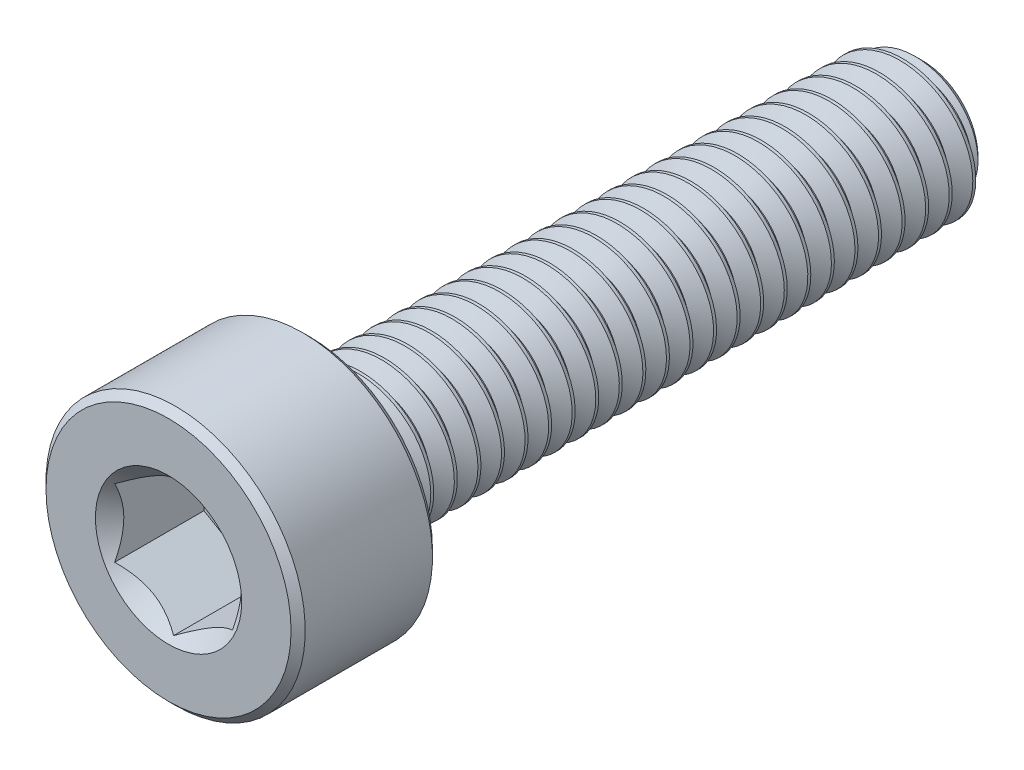
SolidWorks part; units mm, degrees
ref_plane "Front Plane" through (0, 0, 0) normal (0, 0, 1) x (1, 0, 0)
ref_plane "Top Plane" through (0, 0, 0) normal (0, 1, 0) x (1, 0, 0)
ref_plane "Right Plane" through (0, 0, 0) normal (1, 0, 0) x (0, 0, -1)
sketch "Sketch1" plane through (0, 0, 0) normal (1, 0, 0) x (0, 0, -1)
  line L0 (-8, 0) -> (8, 0) construction
  line L1 (8, 0) -> (8, 1.1752) construction
  line L2 (8, 1.1752) -> (7.6752, 1.5) construction
  line L3 (7.6752, 1.5) -> (7.625, 1.5) construction
  line L4 (7.625, 1.5) -> (-5, 1.5) construction
  line L5 (-5, 1.5) -> (-5, 2.75) construction
  line L6 (-5, 2.75) -> (-8, 2.75) construction
  line L7 (-8, 2.75) -> (-8, 0) construction
  line L8 (8, 1.1752) -> (8, 1.5) construction
  line L9 (7.9688, 1.5541) -> (8.2188, 1.1211) construction
  line L10 (8.2188, 1.1211) -> (8.4688, 1.5541) construction
  line L11 (8.4688, 1.5541) -> (7.9688, 1.5541) construction
  line L12 (8.2188, 1.5541) -> (8.2188, 1.5) construction
  line L13 (8.2188, 1.1211) -> (8.2188, 1.1752) construction
  line L14 (8.1875, 1.1752) -> (8.25, 1.1752) construction
  line L15 (8, 1.5) -> (8.4375, 1.5) construction
  line L16 (7.9844, 1.5271) -> (8.4531, 1.5271) construction
  line L17 (8, 0) -> (8, -1.5) construction
  line L18 (-5.15, 2.75) -> (-5, 2.6) construction
  line L19 (-7.85, 2.75) -> (-8, 2.6) construction
  line L20 (-5, 1.5) -> (-5, 0) construction
  line L21 (-5, 0.75) -> (-0.6667, 0.75) construction
  line L22 (-0.6667, 0.75) -> (3.6667, 0.75) construction
  line L23 (3.6667, 0.75) -> (8, 0.75) construction
  line L24 (-0.6667, 0.75) -> (-0.6667, 1.5) construction
  line L25 (-0.6667, 1.5) -> (-0.6667, 2.75) construction
  line L26 (3.6667, 0.75) -> (3.6667, 2.75) construction
  point P0 (-8, 1.25)
  point P3 (6.75, 1.5)
  point P4 (0, 0)
  point P18 (3.6667, 1.5)
  point P22 (8.2188, 1.1752)
  point P24 (7.625, 1.5)
  point P25 (8.2188, 1.5)
  point P28 (8.2188, 1.5271)
  point P29 (6.75, -1.5)
  point P30 (-0.6667, 1.5)
  point P31 (-6.5, 2.75)
  point P37 (-5.525, 2.75)
  point P38 (-7.775, 2.75)
  point P45 (-0.6667, 0.75)
  point P46 (3.6667, 0.75)
  dimension "D2" = 0.0625
  dimension "D7" = 0.15
  dimension "D8" = 0.15
  dimension "D9" = 0.15
  dimension "D10" = 0.075
  dimension "D11" = 0.375
  dimension "Drive Size" = 2.5
  dimension "Head Diameter" = 5.5
  dimension "Head Height" = 3
  dimension "Thread Pitch" = 0.5
  dimension "Thread Dia" = 3
  dimension "Length" = 13
  dimension "D12" = 0.375
  dimension "D4" = 1.25
  dimension "D3" = 45
sketch "Sketch2" plane through (0, 0, 0) normal (1, 0, 0) x (0, 0, -1)
  line L0 (-8, 0) -> (-8, 2.6)
  line L1 (-7.85, 2.75) -> (-5.15, 2.75)
  line L2 (-5, 2.6) -> (-5, 1.65)
  line L4 (7.6752, 1.5) -> (8, 1.1752)
  line L5 (8, 1.1752) -> (8, 0)
  line L6 (-5, 2.75) -> (-8, 2.75) construction
  line L7 (8, 0) -> (-8, 0)
  line L8 (-7.85, 2.75) -> (-8, 2.6) construction
  line L10 (-7.85, 2.75) -> (-8, 2.6)
  line L14 (-5.15, 2.75) -> (-5, 2.6) construction
  line L16 (-5.15, 2.75) -> (-5, 2.6)
  line L17 (-5, 1.5) -> (-5, 2.75) construction
  line L19 (-4.85, 1.5) -> (7.6752, 1.5)
  line L20 (7.625, 1.5) -> (-5, 1.5) construction
  arc A1 (-5, 1.65) -> (-4.85, 1.5) centre (-4.85, 1.65) ccw
  dimension "D3" = 0.15
revolve "Revolve1" add sketch "Sketch2" angle 360 about L7
sketch "Sketch3" plane through (0, 0, 8) normal (0, 0, 1) x (1, 0, 0)
  line L1 (1.25, -0.7217) -> (1.25, 0.7217)
  line L2 (1.25, 0.7217) -> (0, 1.4434)
  line L3 (0, 1.4434) -> (-1.25, 0.7217)
  line L4 (-1.25, 0.7217) -> (-1.25, -0.7217)
  line L5 (-1.25, -0.7217) -> (0, -1.4434)
  line L6 (0, -1.4434) -> (1.25, -0.7217)
  circle A0 centre (0, 0) radius 1.25 construction
  circle A1 centre (0, 0) radius 2.75 construction
  circle A2 centre (0, 0) radius 2.75 construction
  circle A3 centre (0, 0) radius 1.4434 construction
  point P13 (0, 0)
  dimension "D1" = 2.8868
extrude "Cut-Extrude1" cut sketch "Sketch3" against normal offset from surface (2 mm away) 1 up to face at (0, 2.6, 5)
sketch "Sketch4" plane through (0, 0, 8) normal (0, 0, 1) x (1, 0, 0)
  circle A0 centre (0, 0) radius 1.5516
  dimension "D1" = 3.1033
extrude "Cut-Extrude2" cut sketch "Sketch4" against normal up to vertex (1.5 mm away) draft 45 up to point (0, 2.75, 6.5)
sketch "Sketch11" plane through (0, 0, 0) normal (1, 0, 0) x (0, 0, -1)
  line L0 (-8, 0) -> (8, 0) construction
  line L1 (-8, 0) -> (8, 0) construction
  line L2 (-2.5625, 0) -> (-2.5625, 1.5) construction
  line L3 (7.625, 1.5) -> (-5, 1.5) construction
  line L4 (5.5625, 0) -> (5.5625, 1.5) construction
  line L6 (8, 1.1752) -> (8, 1.5) construction
  point P2 (-2.5625, 0)
  point P3 (5.5625, 0)
  dimension "D1" = 2.4375
  dimension "D2" = 2.4375
sketch "Sketch6" plane through (0, 0, -8) normal (0, 0, -1) x (-1, 0, 0)
  circle A0 centre (0, 0) radius 1.5
curve "Helix/Spiral1" pitch 0.5 height 13.5 radius 1.5 centre (0, 0, -8) axis (0, 0, 1) start towards (0, 1, 0)
sketch "Sketch10" plane through (0, 0, 0) normal (1, 0, 0) x (0, 0, -1)
  line L0 (-4.85, -2.75) -> (-4.85, 2.75)
  line L5 (-8, 0) -> (8, 0) construction
  line L6 (-4.85, 1.5) -> (-4.85, -1.5) construction
  point P3 (-4.85, 0)
split "Split1" trim tools "Sketch10" bodies to split 106 resulting bodies 114 115
sketch "Sketch7" plane through (0, 0, 0) normal (1, 0, 0) x (0, 0, -1)
  line L0 (7.9844, 1.5271) -> (8.4531, 1.5271)
  line L1 (8.4531, 1.5271) -> (8.25, 1.1752)
  line L2 (8.25, 1.1752) -> (8.1875, 1.1752)
  line L3 (8.1875, 1.1752) -> (7.9844, 1.5271)
sweep "Cut-Sweep1" cut profiles "Sketch7" path "Helix/Spiral1" align with end faces yes
sketch "Sketch8" plane through (0, 0, 0) normal (1, 0, 0) x (0, 0, -1)
  line L0 (-5, 0) -> (-5, 1.5)
  line L1 (-4.85, -1.5) -> (-4.85, 1.5) construction
  line L2 (-5, 1.5) -> (-4.85, 1.5)
  line L4 (-4.85, 1.5) -> (-3.984, 0)
  line L5 (-3.984, 0) -> (-5, 0)
  line L6 (7.625, 1.5) -> (-5, 1.5) construction
  line L7 (-8, 0) -> (8, 0) construction
  dimension "D1" = 60
revolve "Revolve2" add sketch "Sketch8" angle 360 about L5
equation "\"D2@Sketch1\" = \"Thread Pitch@Sketch1\" / 8"
equation "\"D4@Helix/Spiral1\" = \"Thread Pitch@Sketch1\""
equation "\"D7@Sketch1\" = \"Head Height@Sketch1\" * .05"
equation "\"D8@Sketch1\"=\"D7@Sketch1\""
equation "\"D9@Sketch1\"=\"D7@Sketch1\""
equation "\"D10@Sketch1\"=\"D7@Sketch1\"/2"
equation "\"D11@Sketch1\"=\"D10@Sketch1\"*5"
equation "\"D4@Sketch1\"=\"Thread Pitch@Sketch1\"*2.5"
equation "\"D12@Sketch1\"=\"Thread Pitch@Sketch1\"*.75"
equation "\"D3@Helix/Spiral1\"=\"Length@Sketch1\"+\"Thread Pitch@Sketch1\""
equation "\"D3@Sketch2\"=\"Thread Dia@Sketch1\"*0.05"
equation "\"D1@Sketch11\"=\"Length@Sketch1\"*0.1875"
equation "\"D2@Sketch11\"=\"D1@Sketch11\""
equation "\"D1@Sketch4\"=\"D1@Sketch3\"*1.075"
